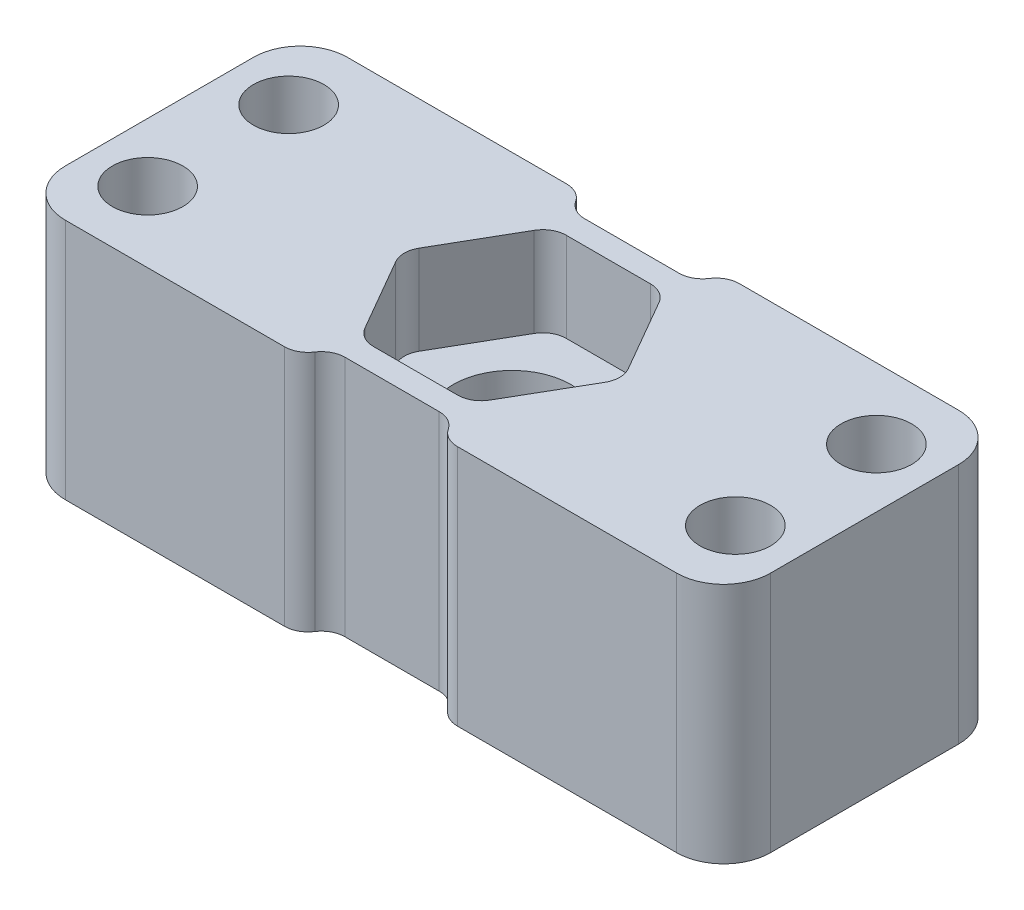
SolidWorks part; units mm, degrees
material "POM"
ref_plane "前视基准面" through (0, 0, 0) normal (0, 0, 1) x (1, 0, 0)
ref_plane "上视基准面" through (0, 0, 0) normal (0, 1, 0) x (1, 0, 0)
ref_plane "右视基准面" through (0, 0, 0) normal (1, 0, 0) x (0, 0, -1)
sketch "草图1" plane through (0, 0, 0) normal (0, 1, 0) x (1, 0, 0)
  line L0 (15, 12) -> (15, 0) construction
  line L1 (0, 0) -> (30, 0)
  line L2 (0, 0) -> (0, 12)
  line L3 (0, 12) -> (30, 12)
  line L4 (30, 0) -> (30, 12)
  line L5 (0, 6) -> (30, 6) construction
  line L6 (18, 11.1) -> (12, 11.1)
  line L7 (18, -0.9) -> (12, -0.9)
  line L8 (18, -0.9) -> (18, 0.9)
  line L9 (18, 0.9) -> (12, 0.9)
  line L10 (12, -0.9) -> (12, 0.9)
  line L11 (18, -0.9) -> (12, 0.9) construction
  line L12 (18, 0.9) -> (12, -0.9) construction
  line L13 (12, 12.9) -> (12, 11.1)
  line L14 (18, 12.9) -> (12, 12.9)
  line L15 (18, 12.9) -> (18, 11.1)
  circle A0 centre (2.5, 9) radius 1.5
  circle A1 centre (27.5, 9) radius 1.5
  circle A2 centre (27.5, 3) radius 1.5
  circle A3 centre (2.5, 3) radius 1.5
  circle A4 centre (15, 6) radius 2.5
  dimension "D3" = 6
  dimension "D4" = 25
  dimension "D5" = 3
  dimension "D7" = 5
  dimension "D8" = 6
  dimension "D1" = 30
  dimension "D2" = 12
  dimension "D6" = 6
  dimension "D9" = 0.9
  dimension "D10" = 6
extrude "凸台-拉伸1" add sketch "草图1" along normal blind 10.3 contours L3 L15 L6 L13 L2 L1 L10 L9 L8 L4 A4 A1 A0 A2 A3 region at (0.3231, 0, -6)
sketch "草图2" plane through (0, 10.3, 0) normal (0, 1, 0) x (1, 0, 0)
  line L0 (15, 16.2) -> (15, 6) construction
  line L1 (30, 0) -> (30, 12) construction
  line L3 (10.2657, 6) -> (12.6329, 1.9)
  line L4 (12.6329, 1.9) -> (17.3671, 1.9)
  line L5 (17.3671, 1.9) -> (19.7343, 6)
  line L6 (19.7343, 6) -> (17.3671, 10.1)
  line L7 (17.3671, 10.1) -> (12.6329, 10.1)
  line L8 (12.6329, 10.1) -> (10.2657, 6)
  line L9 (19.7343, 6) -> (15, 6) construction
  line L10 (18, 11.1) -> (12, 11.1) construction
  circle A0 centre (15, 6) radius 4.1 construction
  point P4 (30, 6)
  point P13 (15, 11.1)
  dimension "D2" = 8.2
extrude "切除-拉伸1" cut sketch "草图2" against normal blind 3.8
fillet "圆角1" radius 2 4 edges at (30, 5.15, 0) (30, 5.15, -12) (0, 5.15, -12) (0, 5.15, 0)
fillet "圆角2" radius 1 6 edges at (17.3671, 8.4, -10.1) (19.7343, 8.4, -6) (17.3671, 8.4, -1.9) (12.6329, 8.4, -1.9) (10.2657, 8.4, -6) (12.6329, 8.4, -10.1)
fillet "圆角3" radius 1 4 edges at (12, 5.15, -0.9) (18, 5.15, -0.9) (12, 5.15, -11.1) (18, 5.15, -11.1)
fillet "圆角4" radius 1 4 edges at (12, 5.15, -12) (18, 5.15, -12) (12, 5.15, 0) (18, 5.15, 0)
